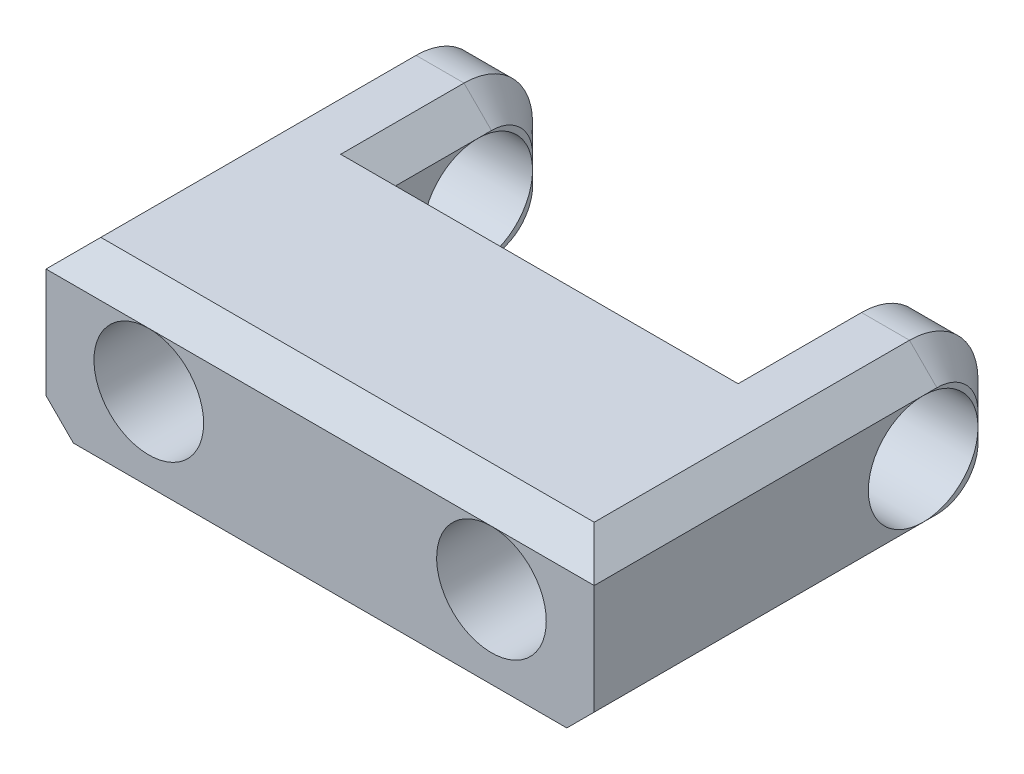
SolidWorks part; units mm, degrees
ref_plane "Front Plane" through (0, 0, 0) normal (0, 0, 1) x (1, 0, 0)
ref_plane "Top Plane" through (0, 0, 0) normal (0, 1, 0) x (1, 0, 0)
ref_plane "Right Plane" through (0, 0, 0) normal (1, 0, 0) x (0, 0, -1)
sketch "Sketch1" plane through (0, 0, 0) normal (0, 1, 0) x (1, 0, 0)
  line L1 (-20, -15) -> (20, -15)
  line L2 (-20, -15) -> (-20, 15)
  line L3 (-20, 15) -> (20, 15)
  line L4 (20, -15) -> (20, 15)
  line L5 (-20, -15) -> (20, 15) construction
  line L6 (-20, 15) -> (20, -15) construction
  point P0 (0, 0)
  dimension "D1" = 40
  dimension "D2" = 30
extrude "Boss-Extrude1" add sketch "Sketch1" along normal blind 12
sketch "Sketch2" plane through (0, 12, 0) normal (0, 1, 0) x (1, 0, 0)
  line L0 (20, 15) -> (-20, 15) construction
  line L1 (-12.5, 3) -> (12.5, 3)
  line L2 (-12.5, 3) -> (-12.5, 15)
  line L3 (-12.5, 15) -> (12.5, 15)
  line L4 (12.5, 3) -> (12.5, 15)
  line L5 (-12.5, 3) -> (12.5, 15) construction
  line L6 (-12.5, 15) -> (12.5, 3) construction
  point P0 (0, 9)
  dimension "D1" = 25
  dimension "D2" = 12.5
  dimension "D3" = 12
extrude "Cut-Extrude1" cut sketch "Sketch2" against normal blind 12
sketch "Sketch3" plane through (20, 0, 0) normal (1, 0, 0) x (0, 0, -1)
  line L0 (15, 12) -> (15, 0) construction
  circle A0 centre (9, 6) radius 4
  dimension "D1" = 6
extrude "Cut-Extrude2" cut sketch "Sketch3" against normal blind 100
fillet "Fillet1" radius 5 4 edges at (-16.25, 0, -15) (-16.25, 12, -15) (16.25, 0, -15) (16.25, 12, -15)
sketch "Sketch4" plane through (0, 0, 15) normal (0, 0, 1) x (1, 0, 0)
  line L0 (-20, 12) -> (-20, 0) construction
  circle A0 centre (-12.5, 6) radius 4
  circle A1 centre (12.5, 6) radius 4
  dimension "D1" = 7.5
  dimension "D2" = 25
extrude "Cut-Extrude3" cut sketch "Sketch4" against normal blind 12.5
chamfer "Chamfer1" distance 2 angle 45 22 edges at (20, 0, 2.5) (-20, 0, 2.5) (20, 1.4645, -13.5355) (-20, 1.4645, -13.5355) (20, 6, -15) (-20, 6, -15) (20, 10.5355, -13.5355) (-20, 10.5355, -13.5355) (20, 12, 2.5) (0, 12, 15) (-20, 12, 2.5) (12.5, 0, -6.5) (-12.5, 0, -6.5) (12.5, 1.4645, -13.5355) (-12.5, 1.4645, -13.5355) (12.5, 6, -15) (-12.5, 6, -15) (12.5, 10.5355, -13.5355) (-12.5, 10.5355, -13.5355) (12.5, 12, -6.5) (0, 12, -3) (-12.5, 12, -6.5)
